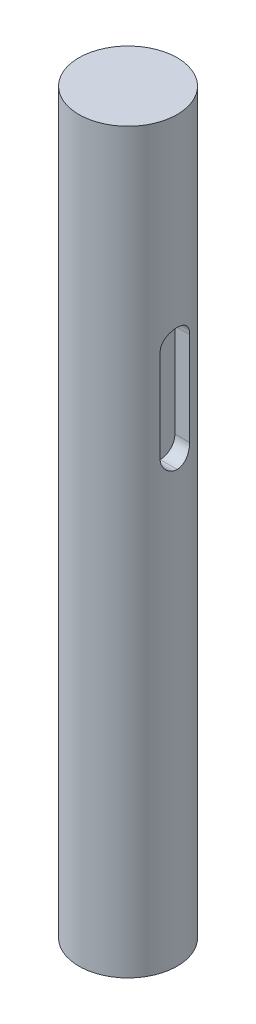
SolidWorks part; units mm, degrees
material "1023 Carbon Steel Sheet (SS)"
ref_plane "Front Plane" through (0, 0, 0) normal (0, 0, 1) x (1, 0, 0)
ref_plane "Top Plane" through (0, 0, 0) normal (0, 1, 0) x (1, 0, 0)
ref_plane "Right Plane" through (0, 0, 0) normal (1, 0, 0) x (0, 0, -1)
ref_axis "Axis1" through (0, -160.1892, 0) along (0, 1, 0)
sketch "Sketch1" plane through (0, 0, 0) normal (0, 0, 1) x (1, 0, 0)
  line L0 (0, -150) -> (10, -150)
  line L1 (0, -160.1892) -> (0, 55) construction
  line L2 (10, -150) -> (10, 0)
  line L5 (0, 0) -> (0, -150)
  line L6 (0, 0) -> (10, 0)
  dimension "D2" = 10
  dimension "D3" = 150
revolve "Revolve1" add sketch "Sketch1" angle 360 about axis through (0, -160.1892, 0) along (0, 1, 0)
ref_plane "keyway center" through (0, -50, 0) normal (0, 1, 0) x (1, 0, 0)
sketch "Sketch2" plane through (0, -50, 0) normal (0, 1, 0) x (1, 0, 0)
  line L0 (9.5394, -3) -> (6.5394, -3)
  line L1 (6.5394, -3) -> (6.5394, 3)
  line L2 (6.5394, 3) -> (9.5394, 3)
  line L3 (1.1819, 0) -> (-0.7441, 0) construction
  circle A0 centre (0, 0) radius 10 construction
  arc A1 (9.5394, -3) -> (9.5394, 3) centre (0, 0) ccw
  point P7 (0, 0)
  dimension "D1" = 6
  dimension "D2" = 3
extrude "Cut-Extrude1" cut sketch "Sketch2" against normal mid plane 25
fillet "Fillet1" radius 3 4 edges at (8.0394, -62.5, -3) (8.0394, -62.5, 3) (8.0394, -37.5, -3) (8.0394, -37.5, 3)
